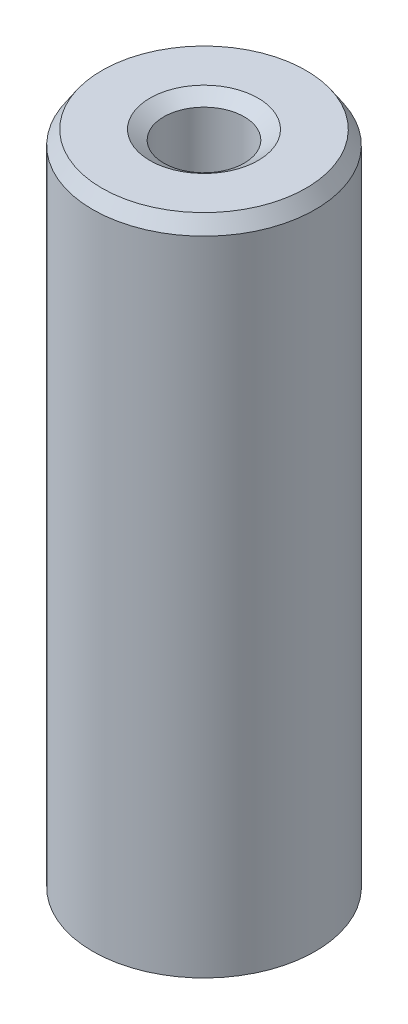
SolidWorks part; units mm, degrees
ref_plane "Front Plane" through (0, 0, 0) normal (0, 0, 1) x (1, 0, 0)
ref_plane "Top Plane" through (0, 0, 0) normal (0, 1, 0) x (1, 0, 0)
ref_plane "Right Plane" through (0, 0, 0) normal (1, 0, 0) x (0, 0, -1)
sketch "Sketch1" plane through (0, 0, 0) normal (0, 1, 0) x (1, 0, 0)
  circle A0 centre (0, 0) radius 5
  dimension "SLEEVE_OD" = 10
extrude "Boss-Extrude1" add sketch "Sketch1" along normal blind 29.9059
sketch "Sketch2" plane through (0, 0, 0) normal (0, 1, 0) x (1, 0, 0)
  circle A0 centre (0, 0) radius 1.807
  dimension "BORE_D" = 3.614
extrude "Cut-Extrude1" cut sketch "Sketch2" along normal through all
chamfer "Chamfer1" distance 0.6244 angle 33.578 4 edges at (0, 29.9059, 1.807) (0, 0, 1.807) (0, 0, 5) (0, 29.9059, 5) first distance on face at (0, 29.9059, 1.807) first distance on face at (0, 0, 1.807) first distance on face at (0, 29.9059, 5)
